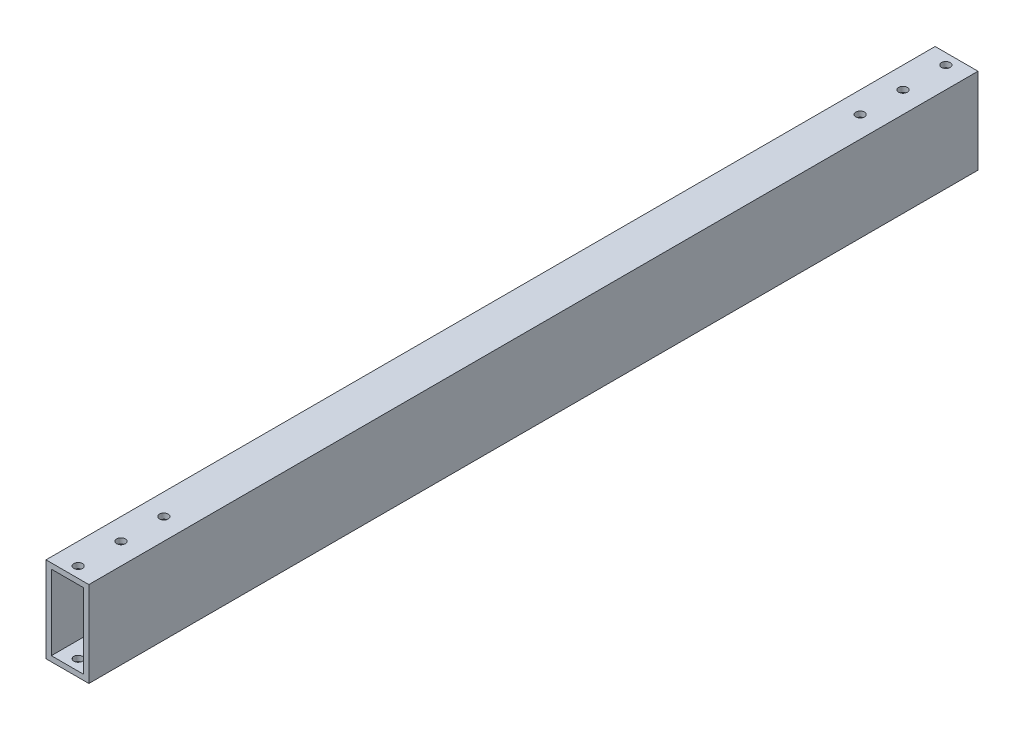
SolidWorks part; units mm, degrees
material "6061-T6 (SS)"
ref_plane "Front" through (0, 0, 0) normal (0, 0, 1) x (1, 0, 0)
ref_plane "Top" through (0, 0, 0) normal (0, 1, 0) x (1, 0, 0)
ref_plane "Right" through (0, 0, 0) normal (1, 0, 0) x (0, 0, -1)
sketch "Sketch1" plane through (0, 0, 0) normal (0, 0, 1) x (1, 0, 0)
  line L1 (-12.7, -25.4) -> (12.7, -25.4)
  line L2 (-12.7, -25.4) -> (-12.7, 25.4)
  line L3 (-12.7, 25.4) -> (12.7, 25.4)
  line L4 (12.7, -25.4) -> (12.7, 25.4)
  line L5 (-12.7, -25.4) -> (12.7, 25.4) construction
  line L6 (-12.7, 25.4) -> (12.7, -25.4) construction
  point P0 (0, 0)
  dimension "D1" = 25.4
  dimension "D2" = 50.8
extrude "Extrude-Thin1" add sketch "Sketch1" along normal blind 527.05 thin thin type one direction reverse wall 3.175
hole_wizard "#10 Clearance Hole1" positions "Sketch2" profile "Sketch3" hole size "#10" standard "ANSI Inch" end condition through all
sketch "Sketch2" plane through (0, 25.4, 0) normal (0, 1, 0) x (1, 0, 0)
  line L0 (12.7, -527.05) -> (-12.7, -527.05) construction
  line L1 (-12.7, -527.05) -> (-12.7, 0) construction
  point P0 (0, -520.7)
  point P2 (0, -495.3)
  point P4 (0, -469.9)
  point P13 (0, -6.35)
  point P15 (0, -31.75)
  point P17 (0, -57.15)
  dimension "D1" = 6.35
  dimension "D2" = 25.4
  dimension "D3" = 25.4
  dimension "D4" = 12.7
  dimension "D5" = 6.35
  dimension "D6" = 25.4
  dimension "D7" = 25.4
sketch "Sketch3" plane through (0, 25.4, 520.7) normal (1, 0, 0) x (0, 0, 1)
  line L0 (0, 0) -> (0, 50.8)
  line L1 (0, 50.8) -> (2.5527, 50.8)
  line L2 (2.5527, 50.8) -> (2.5527, 0)
  line L5 (2.5527, 0) -> (0, 0)
  line L11 (0, -6.35) -> (0, 107.95) construction
  dimension "Thru Hole Dia." = 5.1054
  dimension "Thru Hole Depth" = 50.8
